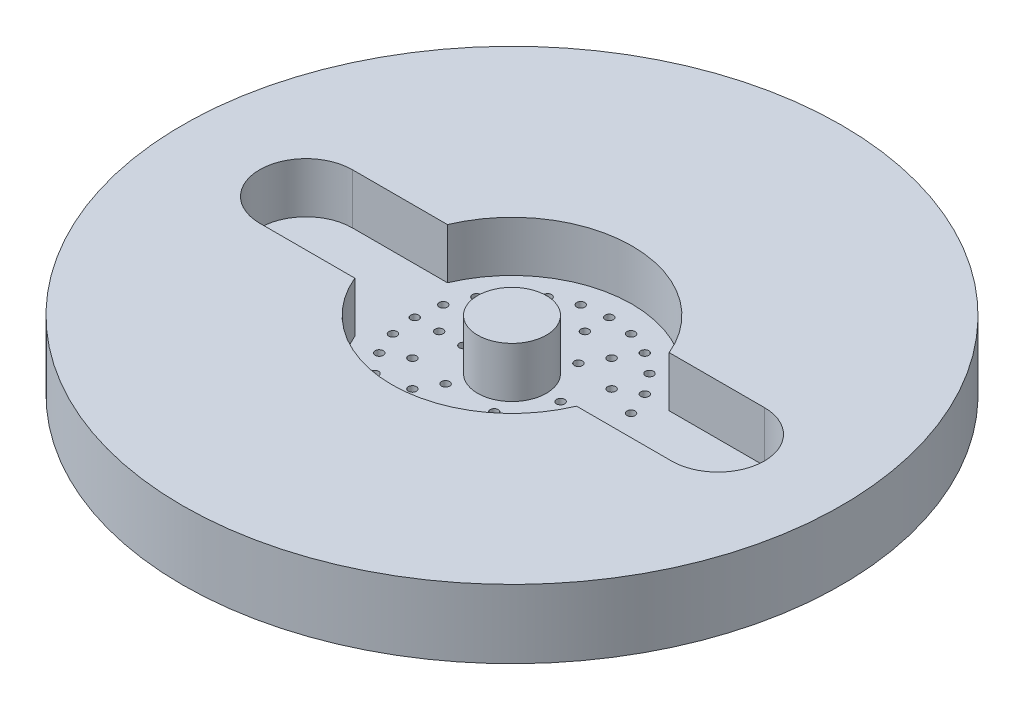
SolidWorks part; units mm, degrees
ref_plane "Front Plane" through (0, 0, 0) normal (0, 0, 1) x (1, 0, 0)
ref_plane "Top Plane" through (0, 0, 0) normal (0, 1, 0) x (1, 0, 0)
ref_plane "Right Plane" through (0, 0, 0) normal (1, 0, 0) x (0, 0, -1)
ref_axis "Axial" through (0, 0.508, 0) along (0, -1, 0)
ref_plane "Bottom Plane" through (0, -12.7, 0) normal (0, 1, 0) x (1, 0, 0)
sketch "Sketch1" plane through (0, 0, 0) normal (0, 1, 0) x (1, 0, 0)
  circle A0 centre (0, 0) radius 60.96
  dimension "D1" = 121.92
extrude "Billet" add sketch "Sketch1" against normal blind 12.7
sketch "Sketch4" plane through (0, -12.7, 0) normal (0, 1, 0) x (1, 0, 0)
  line L0 (0, 37.2675) -> (0, -28.2573) construction
  line L1 (-38.2015, 0) -> (37.6086, 0) construction
  circle A0 centre (8.9916, 0) radius 0.7493
  circle A1 centre (13.4874, 0) radius 0.7493
  circle A2 centre (17.9832, 0) radius 0.7493
  dimension "D1" = 1.4986
  dimension "D3" = 4.4958
  dimension "D4" = 4.4958
  dimension "D2" = 8.9916
extrude "First Kerosene Outlet" cut sketch "Sketch4" along normal through all and the other way through all
sketch "Sketch15" plane through (0, -12.7, 0) normal (0, 1, 0) x (1, 0, 0)
  circle A0 centre (0, 0) radius 57.15
  circle A1 centre (0, 0) radius 59.69
  dimension "D1" = 114.3
  dimension "D2" = 119.38
sketch "Sketch16" plane through (0, 0, 0) normal (0, 1, 0) x (1, 0, 0)
  circle A0 centre (0, 0) radius 59.69
  circle A1 centre (0, 0) radius 57.15
  dimension "D1" = 119.38
  dimension "D2" = 114.3
pattern_circular "Primary Holes" count 6 over 360 about axis through (0, 0.508, 0) along (0, -1, 0) of "First Kerosene Outlet"
pattern_circular "Second ring" count 12 over 360 about axis through (0, 0.508, 0) along (0, -1, 0) skipping 2, 4, 6, 8, 10 of face at (13.4874, 0, 0.7493)
pattern_circular "Third Ring" count 24 over 360 about axis through (0, 0.508, 0) along (0, -1, 0) skipping 4, 8, 12, 16, 20 of face at (17.9832, 0, 0.7493)
sketch "Sketch18" plane through (0, 0, 0) normal (0, 1, 0) x (1, 0, 0)
  line L0 (-47.0718, 0) -> (54.8652, 0) construction
  line L1 (0, 40.3695) -> (0, -40.0578) construction
  line L2 (-38.1, 8.575) -> (-20.5041, 8.575)
  line L3 (-38.1, -8.575) -> (-20.5041, -8.575)
  line L4 (38.1, 8.575) -> (20.5041, 8.575)
  line L5 (38.1, -8.575) -> (20.5041, -8.575)
  arc A0 (-20.5041, -8.575) -> (20.5041, -8.575) centre (0, 0) ccw
  arc A1 (-38.1, 8.575) -> (-38.1, -8.575) centre (-38.1, 0) ccw
  arc A2 (38.1, 8.575) -> (38.1, -8.575) centre (38.1, 0) cw
  arc A3 (20.5041, 8.575) -> (-20.5041, 8.575) centre (0, 0) ccw
  dimension "D1" = 44.45
  dimension "D2" = 17.1501
  dimension "D3" = 38.1
extrude "Kerosene Well" cut sketch "Sketch18" against normal blind 9.3218
sketch "Sketch17" plane through (0, 0, 0) normal (0, 1, 0) x (1, 0, 0)
  circle A0 centre (0, 0) radius 6.35
  dimension "D1" = 12.7
extrude "Boss-Extrude1" add sketch "Sketch17" along normal blind 2.54 and the other way up to next
sketch "Sketch19" plane through (0, 2.54, 0) normal (0, 1, 0) x (1, 0, 0)
  circle A0 centre (0, 0) radius 6.35
  dimension "D1" = 12.7
extrude "Lox Tower" cut sketch "Sketch19" against normal blind 2.54
sketch "Sketch20" plane through (0, 0, 0) normal (0, 1, 0) x (1, 0, 0)
  line L0 (0, 68.1298) -> (0, -73.4056) construction
  line L1 (-6.985, 0) -> (6.985, 0) construction
  circle A0 centre (0, 25.4) radius 1.1906
  circle A1 centre (0, -25.4) radius 1.1906
  circle A2 centre (0, 50.8) radius 1.1906
  circle A3 centre (0, -50.8) radius 1.1906
  dimension "D1" = 2.3813
  dimension "D3" = 2.3813
  dimension "D2" = 25.4
  dimension "D4" = 50.8
